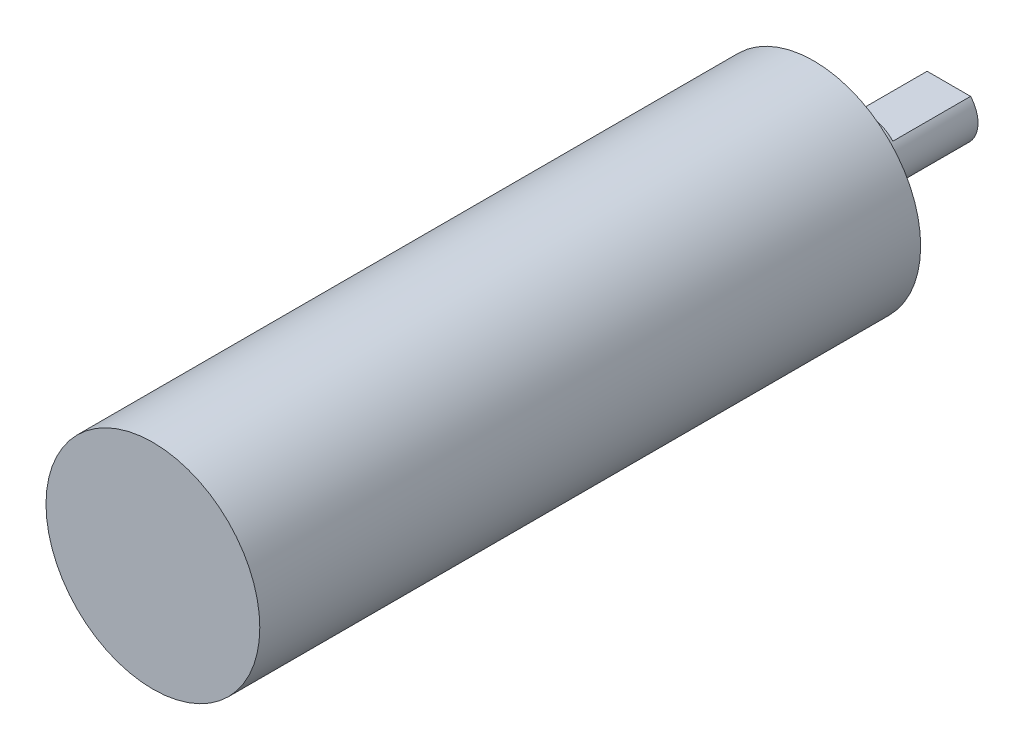
SolidWorks part; units mm, degrees
ref_plane "Front Plane" through (0, 0, 0) normal (0, 0, 1) x (1, 0, 0)
ref_plane "Top Plane" through (0, 0, 0) normal (0, 1, 0) x (1, 0, 0)
ref_plane "Right Plane" through (0, 0, 0) normal (1, 0, 0) x (0, 0, -1)
sketch "Sketch1" plane through (0, 0, 0) normal (0, 0, 1) x (1, 0, 0)
  circle A0 centre (0, 0) radius 11
  dimension "D1" = 22
extrude "Boss-Extrude1" add sketch "Sketch1" along normal blind 68
sketch "Sketch2" plane through (0, 0, 68) normal (0, 0, 1) x (1, 0, 0)
  point P0 (0, 0)
sketch "Sketch3" plane through (0, 0, 0) normal (0, 0, 1) x (1, 0, 0)
  circle A0 centre (0, 0) radius 6
  dimension "D1" = 12
extrude "Boss-Extrude2" add sketch "Sketch3" against normal blind 3.5
sketch "Sketch4" plane through (0, 0, -3.5) normal (0, 0, -1) x (-1, 0, 0)
  circle A0 centre (0, 0) radius 3
  dimension "D1" = 6
extrude "Boss-Extrude3" add sketch "Sketch4" along normal blind 10.4
sketch "Sketch5" plane through (0, 0, -13.9) normal (0, 0, -1) x (-1, 0, 0)
  line L0 (-2.2361, 2) -> (2.2361, 2)
  line L1 (0, 2) -> (0, 3) construction
  circle A0 centre (0, 0) radius 3 construction
  arc A1 (2.2361, 2) -> (-2.2361, 2) centre (0, 0) ccw
  dimension "D1" = 1
extrude "Cut-Extrude1" cut sketch "Sketch5" against normal blind 8
